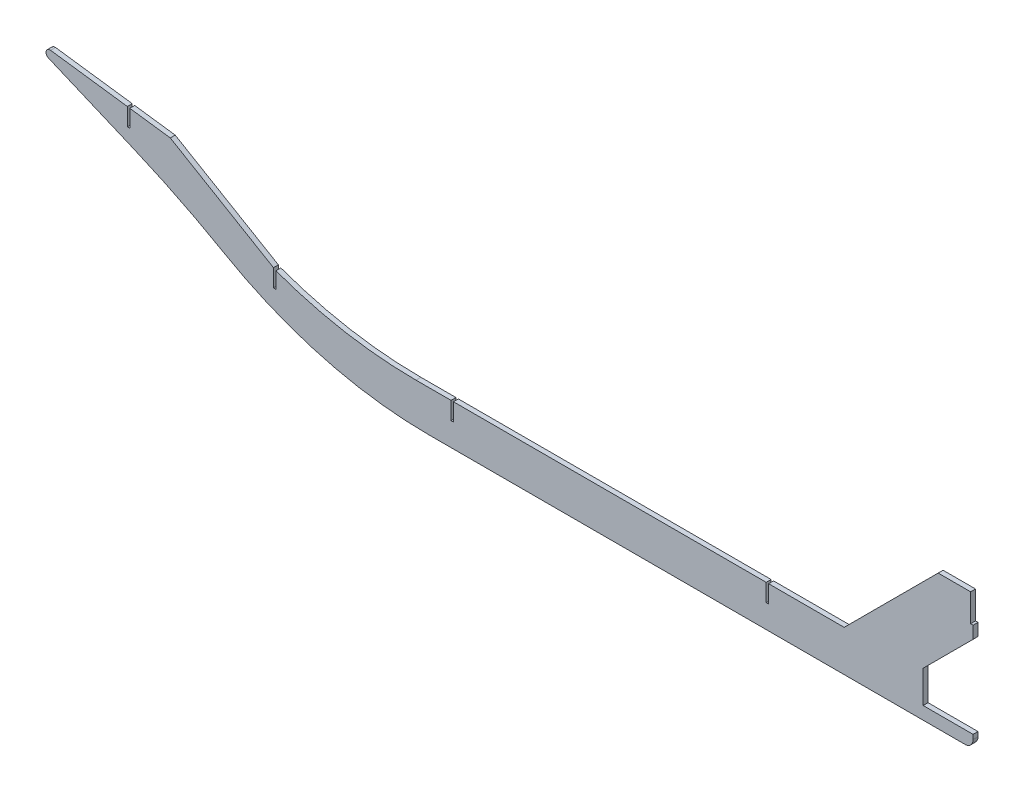
SolidWorks part; units mm, degrees
ref_plane "Plan de face" through (0, 0, 0) normal (0, 0, 1) x (1, 0, 0)
ref_plane "Plan de dessus" through (0, 0, 0) normal (0, 1, 0) x (1, 0, 0)
ref_plane "Plan de droite" through (0, 0, 0) normal (1, 0, 0) x (0, 0, -1)
sketch "Esquisse2" plane through (0, 0, 0) normal (0, 0, 1) x (1, 0, 0)
  line L0 (0, 0) -> (-800, 0)
  line L4 (0, 115.9784) -> (-60.968, 55.0104)
  line L5 (-60.968, 55.0104) -> (-60.968, 15.5486)
  line L6 (-60.968, 15.5486) -> (0, 15.5486)
  line L7 (0, 15.5486) -> (0, 0)
  line L8 (-980.0867, 156.0759) -> (-854.0929, 81.9045)
  line L9 (-799.8971, 50) -> (-637.3335, 50)
  line L10 (-157.3802, 50) -> (-42.62, 164.7602)
  line L11 (-42.62, 164.7602) -> (-3, 164.7602)
  line L13 (-800, 0) -> (-963.9935, 96.5414)
  line L14 (-963.9935, 96.5414) -> (-1163.1175, 180.6367)
  line L15 (-1163.1175, 180.6367) -> (-1032.509, 163.1104)
  line L16 (-1032.509, 163.1104) -> (-1032.509, 141.6104)
  line L17 (-1032.509, 141.6104) -> (-1029.509, 141.6104)
  line L18 (-1029.509, 141.6104) -> (-1029.509, 162.7079)
  line L19 (-1029.509, 162.7079) -> (-980.0867, 156.0759)
  line L20 (-854.0929, 81.9045) -> (-854.0929, 60.4045)
  line L21 (-854.0929, 60.4045) -> (-851.0929, 60.4045)
  line L22 (-851.0929, 60.4045) -> (-851.0929, 80.1385)
  line L23 (-851.0929, 80.1385) -> (-799.8971, 50)
  line L24 (-637.3335, 50) -> (-637.3335, 28.5)
  line L25 (-637.3335, 28.5) -> (-634.3335, 28.5)
  line L26 (-634.3335, 28.5) -> (-634.3335, 50)
  line L27 (-634.3335, 50) -> (-252.5462, 50)
  line L28 (-252.5462, 50) -> (-252.5462, 28.5)
  line L29 (-252.5462, 28.5) -> (-249.5462, 28.5)
  line L30 (-249.5462, 28.5) -> (-249.5462, 50)
  line L31 (-249.5462, 50) -> (-157.3802, 50)
  line L33 (-3, 130.9784) -> (-3, 164.7602)
  line L34 (0, 115.9784) -> (0, 130.9784)
  line L35 (0, 130.9784) -> (-3, 130.9784)
  dimension "D1" = 800
  dimension "D2" = 50
  dimension "D3" = 3
  dimension "D4" = 21.5
  dimension "D5" = 3
  dimension "D6" = 21.5
  dimension "D7" = 3
  dimension "D8" = 21.5
  dimension "D9" = 3
  dimension "D10" = 21.5
  dimension "D11" = 15
extrude "Boss.-Extru.1" add sketch "Esquisse2" along normal blind 6
fillet "Congé1" radius 1000 1 edges at (-963.9935, 96.5414, 3)
fillet "Congé2" radius 500 1 edges at (-800, 0, 3)
fillet "Congé4" radius 10 1 edges at (0, 0, 3)
fillet "Congé5" radius 5 1 edges at (-1163.1175, 180.6367, 3)
fillet "Congé6" radius 500 1 edges at (-799.8971, 50, 3)
